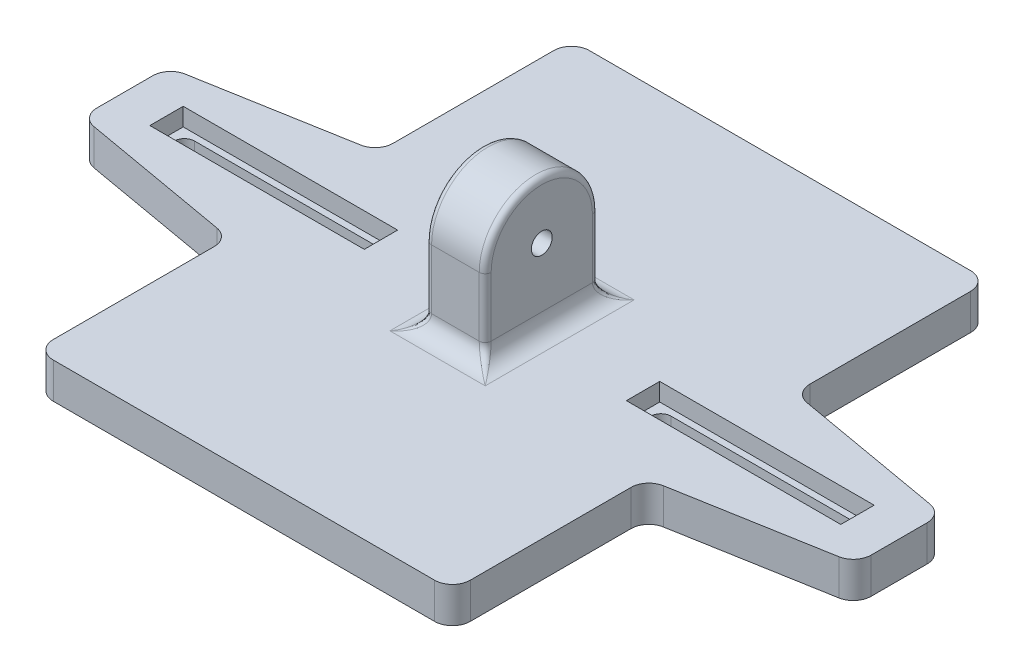
SolidWorks part; units mm, degrees
ref_plane "Alzado" through (0, 0, 0) normal (0, 0, 1) x (1, 0, 0)
ref_plane "Planta" through (0, 0, 0) normal (0, 1, 0) x (1, 0, 0)
ref_plane "Vista lateral" through (0, 0, 0) normal (1, 0, 0) x (0, 0, -1)
sketch "Croquis1" plane through (0, 0, 0) normal (0, 1, 0) x (1, 0, 0)
  line L0 (-35, 0) -> (35, 0) construction
  line L1 (-35, -45) -> (35, -45)
  line L2 (-35, -45) -> (-35, -12.5)
  line L3 (-35, 45) -> (35, 45)
  line L4 (35, -45) -> (35, -12.5)
  line L5 (-35, -45) -> (35, 45) construction
  line L6 (-35, 45) -> (35, -45) construction
  line L7 (-35, 12.5) -> (-65, 7.2102)
  line L8 (-65, 7.2102) -> (-65, -7.2102)
  line L9 (-65, -7.2102) -> (-35, -12.5)
  line L10 (0, 0) -> (0, 45) construction
  line L11 (-55, 0) -> (-25, 0) construction
  line L12 (-55, 1.7) -> (-25, 1.7)
  line L13 (-55, -1.7) -> (-25, -1.7)
  line L14 (-35, 12.5) -> (-35, 45)
  line L15 (55, 0) -> (25, 0) construction
  line L16 (55, 1.7) -> (25, 1.7)
  line L17 (55, -1.7) -> (25, -1.7)
  line L18 (65, -7.2102) -> (35, -12.5)
  line L19 (65, 7.2102) -> (65, -7.2102)
  line L20 (35, 12.5) -> (65, 7.2102)
  line L21 (35, 12.5) -> (35, 45)
  arc A0 (-55, 1.7) -> (-55, -1.7) centre (-55, 0) ccw
  arc A1 (-25, -1.7) -> (-25, 1.7) centre (-25, 0) ccw
  arc A2 (55, 1.7) -> (55, -1.7) centre (55, 0) cw
  arc A3 (25, -1.7) -> (25, 1.7) centre (25, 0) cw
  point P0 (0, 0)
  point P16 (-40, 0)
  point P23 (40, 0)
  point P32 (-38.7535, 9.9078)
  point P33 (0, 0)
  dimension "D3" = 1.7
  dimension "D1" = 70
  dimension "D2" = 90
  dimension "D4" = 30
  dimension "D5" = 30
  dimension "D6" = 80
  dimension "D7" = 40
  dimension "D8" = 25
extrude "Saliente-Extruir1" add sketch "Croquis1" along normal blind 6
sketch "Croquis3" plane through (0, 0, 0) normal (1, 0, 0) x (0, 0, -1)
  line L0 (-9.5, 6) -> (-9.5, 19)
  line L1 (-45, 6) -> (-12.5, 6) construction
  line L2 (9.5, 19) -> (9.5, 6)
  line L3 (12.5, 6) -> (45, 6) construction
  line L4 (9.5, 6) -> (-9.5, 6)
  arc A0 (-9.5, 19) -> (9.5, 19) centre (0, 19) cw
  circle A1 centre (0, 19) radius 1.75
  dimension "D1" = 9.5
  dimension "D3" = 3.5
  dimension "D2" = 13
extrude "Saliente-Extruir2" add sketch "Croquis3" along normal mid plane 10
fillet "Redondeo1" radius 3 12 edges at (-35, 3, 45) (-65, 3, 7.2102) (-35, 3, 12.5) (-65, 3, -7.2102) (-35, 3, -12.5) (35, 3, 12.5) (35, 3, 45) (65, 3, 7.2102) (65, 3, -7.2102) (35, 3, -12.5) (35, 3, -45) (-35, 3, -45)
fillet "Redondeo2" radius 3 4 edges at (0, 6, -9.5) (5, 6, 0) (0, 6, 9.5) (-5, 6, 0)
fillet "Redondeo3" radius 1 10 edges at (-5.8787, 6.8787, -10.3787) (-5, 14, -9.5) (-5.8787, 6.8787, 10.3787) (-5, 14, 9.5) (5.8787, 6.8787, -10.3787) (5, 14, -9.5) (5.8787, 6.8787, 10.3787) (5, 14, 9.5) (-5, 28.5, 0) (5, 28.5, 0)
sketch "Croquis5" plane through (0, 6, 0) normal (0, 1, 0) x (1, 0, 0)
  line L0 (-40, 1.7) -> (-40, -1.7) construction
  line L1 (-25, 1.7) -> (-55, 1.7) construction
  line L2 (-55, -1.7) -> (-25, -1.7) construction
  line L3 (40, 1.7) -> (40, -1.7) construction
  line L4 (55, 1.7) -> (25, 1.7) construction
  line L5 (25, -1.7) -> (55, -1.7) construction
  line L6 (0, 0) -> (0, 9.5) construction
  line L7 (-58, -2.8) -> (-22, -2.8)
  line L8 (-58, -2.8) -> (-58, 2.8)
  line L9 (-58, 2.8) -> (-22, 2.8)
  line L10 (-22, -2.8) -> (-22, 2.8)
  line L11 (-58, -2.8) -> (-22, 2.8) construction
  line L12 (-58, 2.8) -> (-22, -2.8) construction
  line L13 (4, 9.5) -> (-4, 9.5) construction
  line L14 (58, 2.8) -> (22, 2.8)
  line L15 (22, -2.8) -> (22, 2.8)
  line L16 (58, -2.8) -> (22, -2.8)
  line L17 (58, -2.8) -> (58, 2.8)
  point P12 (-40, 0)
  dimension "D1" = 5.6
  dimension "D2" = 36
extrude "Cortar-Extruir1" cut sketch "Croquis5" against normal blind 3
